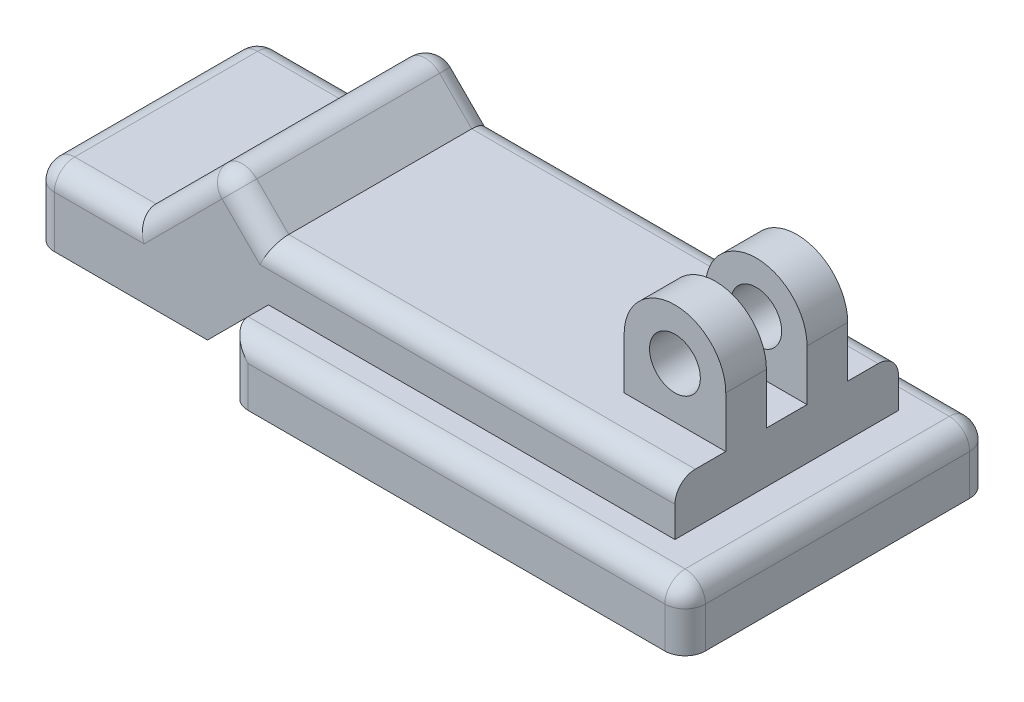
SolidWorks part; units mm, degrees
ref_plane "Front Plane" through (0, 0, 0) normal (0, 0, 1) x (1, 0, 0)
ref_plane "Top Plane" through (0, 0, 0) normal (0, 1, 0) x (1, 0, 0)
ref_plane "Right Plane" through (0, 0, 0) normal (1, 0, 0) x (0, 0, -1)
sketch "Sketch2" plane through (0, 0, 0) normal (0, 0, 1) x (1, 0, 0)
  line L0 (-130, -30) -> (-165.3553, -30)
  line L1 (-100, 25) -> (100, 25)
  line L2 (-100, 25) -> (-100, -30)
  line L3 (-100, -30) -> (100, -30)
  line L4 (100, 25) -> (100, -30)
  line L5 (-165.3553, 5.3553) -> (-215.3553, 5.3553)
  line L6 (-100, 25) -> (-87.5, 12.5)
  line L7 (-137.9415, 12.5) -> (-11.8047, 12.5) construction
  line L8 (-87.5, 12.5) -> (-130, -30)
  line L9 (-87.5, 12.5) -> (-122.8553, 47.8553)
  line L10 (-122.8553, 47.8553) -> (-165.3553, 5.3553)
  line L13 (-215.3553, 5.3553) -> (-215.3553, -30)
  line L14 (-215.3553, -30) -> (-165.3553, -30)
  line L16 (100, 0) -> (-100, 0)
  dimension "D1" = 30
  dimension "D2" = 55
  dimension "D3" = 200
  dimension "D4" = 100
  dimension "D5" = 50
  dimension "D6" = 30
  dimension "D7" = 50
extrude "Boss-Extrude1" add sketch "Sketch2" along normal blind 30 contours L16 L4 L1 L6 L8 | L13 L14 L0 L8 L2 L9 L10 L5 | L7 L2 L8 | L2 L7 L6 region at (-152.1356, -1.5817, 0) region at (-95.8333, 8.3333, 0) region at (3.0914, 12.5, 0) region at (-95.8333, 16.6667, 0)
extrude "Boss-Extrude2" add sketch "Sketch2<4>" against normal blind 30 contours L13 L14 L0 L8 L2 L9 L10 L5 | L2 L7 L6 | L16 L4 L1 L6 L8 | L7 L2 L8 region at (-152.1356, -1.5817, 0) region at (-95.8333, 8.3333, 0) region at (3.0914, 12.5, 0) region at (-95.8333, 16.6667, 0)
sketch "Sketch2<4>" plane through (0, 0, 0) normal (0, 0, 1) x (1, 0, 0) same geometry as "Sketch2"
extrude "Boss-Extrude3" add sketch "Sketch2<5>" along normal blind 75 contours L4 L16 L2 L3 region at (0, -15, 0)
sketch "Sketch2<5>" plane through (0, 0, 0) normal (0, 0, 1) x (1, 0, 0) same geometry as "Sketch2"
extrude "Boss-Extrude4" add sketch "Sketch2<6>" against normal blind 75 contours L4 L16 L2 L3 region at (0, -15, 0)
sketch "Sketch2<6>" plane through (0, 0, 0) normal (0, 0, 1) x (1, 0, 0) same geometry as "Sketch2"
sketch3d "3DSketch1"
  point P0 (-94.0634, -0.2654, 30)
ref_plane "Plane1" through (0, 0, 30) normal (0, 0, 1) x (1, 0, 0)
sketch "Sketch3" plane through (0, 0, 30) normal (0, 0, 1) x (1, 0, 0)
  line L0 (100, 25) -> (100, 0) construction
  line L1 (-100, 25) -> (100, 25) construction
  line L3 (100, 25) -> (50, 25)
  line L4 (100, 25) -> (100, 50)
  line L6 (50, 25) -> (50, 50)
  arc A0 (100, 50) -> (50, 50) centre (75, 50) ccw
  circle A1 centre (75, 50) radius 12.5
  dimension "D1" = 50
  dimension "D5" = 25
  dimension "D2" = 25
  dimension "D3" = 25
  dimension "D4" = 50
extrude "Boss-Extrude5" add sketch "Sketch3" against normal blind 20
sketch3d "3DSketch2"
  point P0 (-77.4546, 3.516, -30)
ref_plane "Plane2" through (0, 0, -30) normal (0, 0, -1) x (-1, 0, 0)
sketch "Sketch4" plane through (0, 0, -30) normal (0, 0, -1) x (-1, 0, 0)
  line L0 (-100, 25) -> (-100, 0) construction
  line L1 (100, 25) -> (-100, 25) construction
  line L3 (-100, 25) -> (-50, 25)
  line L4 (-100, 25) -> (-100, 50)
  line L6 (-50, 25) -> (-50, 50)
  arc A0 (-50, 50) -> (-100, 50) centre (-75, 50) ccw
  circle A1 centre (-75, 50) radius 12.5
  dimension "D1" = 25
  dimension "D2" = 50
  dimension "D3" = 25
  dimension "D4" = 25
  dimension "D5" = 50
extrude "Boss-Extrude6" add sketch "Sketch4" against normal blind 20
sketch3d "3DSketch3"
  point P0 (27.8748, 8.5547, -30)
ref_plane "Plane3" through (0, 0, -30) normal (0, 0, -1) x (-1, 0, 0)
sketch "Sketch5" plane through (0, 0, -30) normal (0, 0, -1) x (-1, 0, 0)
  line L0 (122.8553, 47.8553) -> (100, 25)
  line L1 (100, 25) -> (-100, 25)
  line L2 (-100, 25) -> (-100, 0)
  line L3 (-100, 0) -> (100, 0)
  line L4 (100, 0) -> (130, -30)
  line L5 (130, -30) -> (215.3553, -30)
  line L6 (215.3553, -30) -> (215.3553, 5.3553)
  line L7 (215.3553, 5.3553) -> (165.3553, 5.3553)
  line L8 (165.3553, 5.3553) -> (122.8553, 47.8553)
extrude "Boss-Extrude7" add sketch "Sketch5" along normal blind 25
sketch3d "3DSketch4"
  point P0 (-94.295, -8.6276, 30)
ref_plane "Plane4" through (0, 0, 30) normal (0, 0, 1) x (1, 0, 0)
sketch "Sketch6" plane through (0, 0, 30) normal (0, 0, 1) x (1, 0, 0)
  line L0 (-122.8553, 47.8553) -> (-100, 25)
  line L1 (-100, 25) -> (100, 25)
  line L2 (100, 50) -> (100, 0) construction
  line L3 (100, 25) -> (100, 0)
  line L4 (100, 0) -> (-100, 0)
  line L5 (-100, 0) -> (-130, -30)
  line L6 (-130, -30) -> (-215.3553, -30)
  line L7 (-215.3553, -30) -> (-215.3553, 5.3553)
  line L8 (-215.3553, 5.3553) -> (-165.3553, 5.3553)
  line L9 (-165.3553, 5.3553) -> (-122.8553, 47.8553)
extrude "Boss-Extrude8" add sketch "Sketch6" along normal blind 25
sketch3d "3DSketch5"
  point P0 (100, -22.474, -35.69)
ref_plane "Plane5" through (100, 0, 0) normal (1, 0, 0) x (0, 0, -1)
sketch "Sketch7" plane through (100, 0, 0) normal (1, 0, 0) x (0, 0, -1)
  line L1 (-75, -30) -> (75, -30)
  line L2 (-75, -30) -> (-75, 0)
  line L3 (-75, 0) -> (75, 0)
  line L4 (75, -30) -> (75, 0)
extrude "Boss-Extrude9" add sketch "Sketch7" along normal blind 25
fillet "Fillet1" radius 10 19 edges at (-122.8553, 47.8553, 0) (-215.3553, 5.3553, 0) (-215.3553, -12.3223, -55) (-190.3553, 5.3553, -55) (-144.1053, 26.6053, -55) (-111.4277, 36.4277, -55) (0, 25, -55) (-100, -15, -75) (12.5, 0, -75) (-215.3553, -12.3223, 55) (-190.3553, 5.3553, 55) (-144.1053, 26.6053, 55) (-111.4277, 36.4277, 55) (0, 25, 55) (-100, -15, 75) (125, 0, 0) (12.5, 0, 75) (125, -15, -75) (125, -15, 75)
